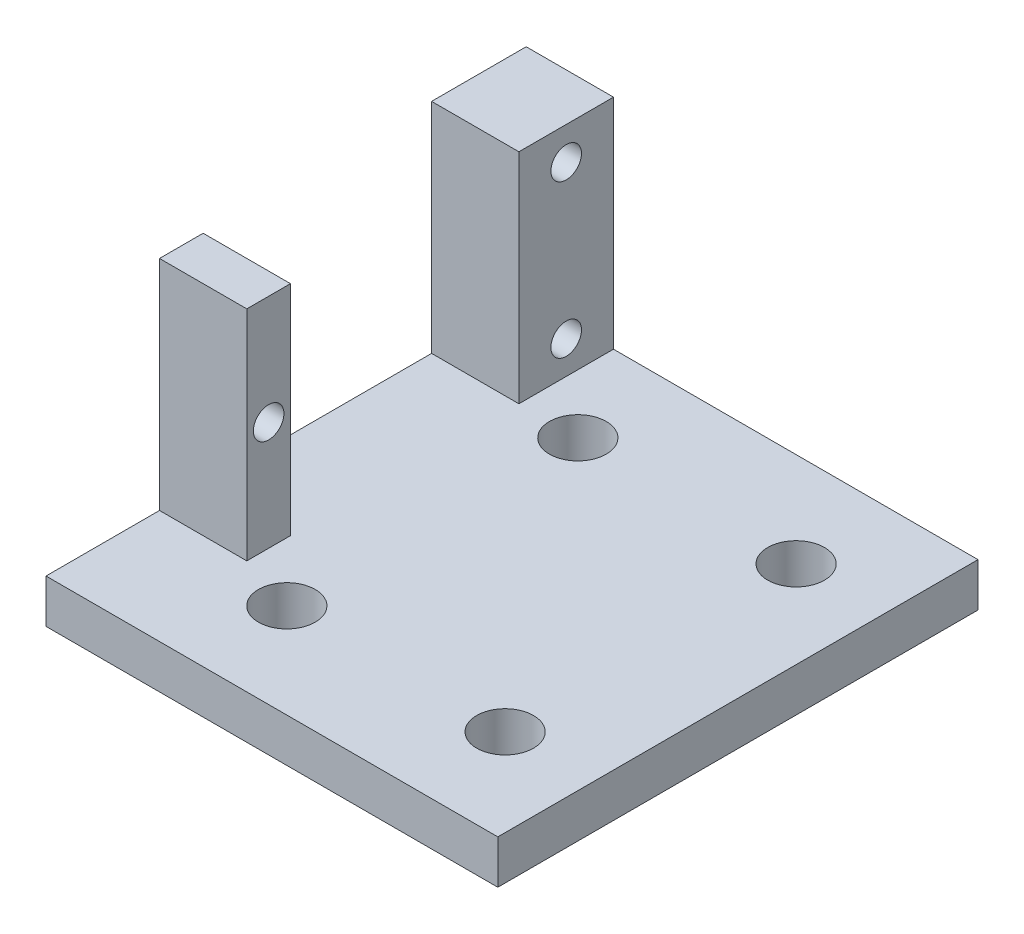
SolidWorks part; units mm, degrees
ref_plane "Front Plane" through (0, 0, 0) normal (0, 0, 1) x (1, 0, 0)
ref_plane "Top Plane" through (0, 0, 0) normal (0, 1, 0) x (1, 0, 0)
ref_plane "Right Plane" through (0, 0, 0) normal (1, 0, 0) x (0, 0, -1)
sketch "Sketch1" plane through (0, 0, 0) normal (0, 1, 0) x (1, 0, 0)
  line L0 (0, 0) -> (0, 23.8066) construction
  line L1 (0, 0) -> (36.6932, 0) construction
  line L2 (-10, 27.5) -> (-10, -27.5) construction
  line L3 (-23.5, 27.5) -> (28.25, 27.5)
  line L4 (-23.5, 27.5) -> (-23.5, -27.5)
  line L5 (-23.5, -27.5) -> (28.25, -27.5)
  line L6 (28.25, 27.5) -> (28.25, -27.5)
  line L7 (-13.5, 27.5) -> (-13.5, -27.5)
  line L8 (-23.5, 16.665) -> (-13.5, 16.665)
  line L9 (-23.5, -9.5) -> (-13.5, -9.5)
  line L10 (-23.5, -14.5) -> (-13.5, -14.5)
  line L11 (-13.5, -16.665) -> (0, -16.665) construction
  circle A0 centre (-6.75, 16.665) radius 3.25
  circle A1 centre (-6.75, -16.665) radius 3.25
  circle A4 centre (18.25, 16.665) radius 3.25
  circle A5 centre (18.25, -16.665) radius 3.25
  point P29 (0, 0)
  point P30 (0, 0)
  point P31 (-6.75, -16.665)
  point P32 (0, 0)
  dimension "D2" = 6.5
  dimension "D5" = 25
  dimension "D1" = 33.33
  dimension "D3" = 10
  dimension "D4" = 55
  dimension "D6" = 10
  dimension "D7" = 37
  dimension "D8" = 5
  dimension "D9" = 10
extrude "Boss-Extrude2" add sketch "Sketch1" along normal blind 5 contours L3 L7 L5 L6 A5 A4 A1 A0 | L4 L9 L7 L8 | L4 L8 L7 L3 | L10 L4 L5 L7 | L4 L10 L7 L9 region at (-18.5, 0, -22.0825) region at (7.4747, 0, 0) region at (-18.5, 0, -3.5825) region at (-18.5, 0, 12) region at (-18.5, 0, 21)
extrude "Boss-Extrude3" add sketch "Sketch1<6>" along normal blind 30 contours L4 L8 L7 L3 | L4 L10 L7 L9 region at (-18.5, 0, -22.0825) region at (-18.5, 0, 12)
sketch "Sketch1<6>" plane through (0, 0, 0) normal (0, 1, 0) x (1, 0, 0) same geometry as "Sketch1"
sketch "Sketch3" plane through (-13.5, 0, 0) normal (1, 0, 0) x (0, 0, -1)
  line L0 (-9.5, 30) -> (-9.5, 5) construction
  line L1 (-9.5, 30) -> (-14.5, 30) construction
  circle A0 centre (-12, 17.5) radius 1.75
  point P4 (-9.5, 17.5)
  point P7 (-12, 30)
  dimension "D1" = 3.5
sketch "Sketch4" plane through (-13.5, 0, 0) normal (1, 0, 0) x (0, 0, -1)
  line L0 (22.0825, 26.25) -> (22.0825, 8.75) construction
  line L1 (27.5, 30) -> (27.5, 5) construction
  line L2 (27.5, 30) -> (16.665, 30) construction
  circle A0 centre (22.0825, 26.25) radius 1.75
  circle A1 centre (22.0825, 8.75) radius 1.75
  point P6 (27.5, 17.5)
  point P7 (22.0825, 17.5)
  point P10 (22.0825, 30)
  dimension "D1" = 3.5
  dimension "D2" = 17.5
sketch "Sketch5" plane through (-13.5, 0, 0) normal (1, 0, 0) x (0, 0, -1)
  line L0 (22.0825, 8.75) -> (22.0825, 26.25) construction
extrude "Cut-Extrude1" cut sketch "Sketch4" against normal through all and the other way through all
extrude "Cut-Extrude2" cut sketch "Sketch3" against normal through all
